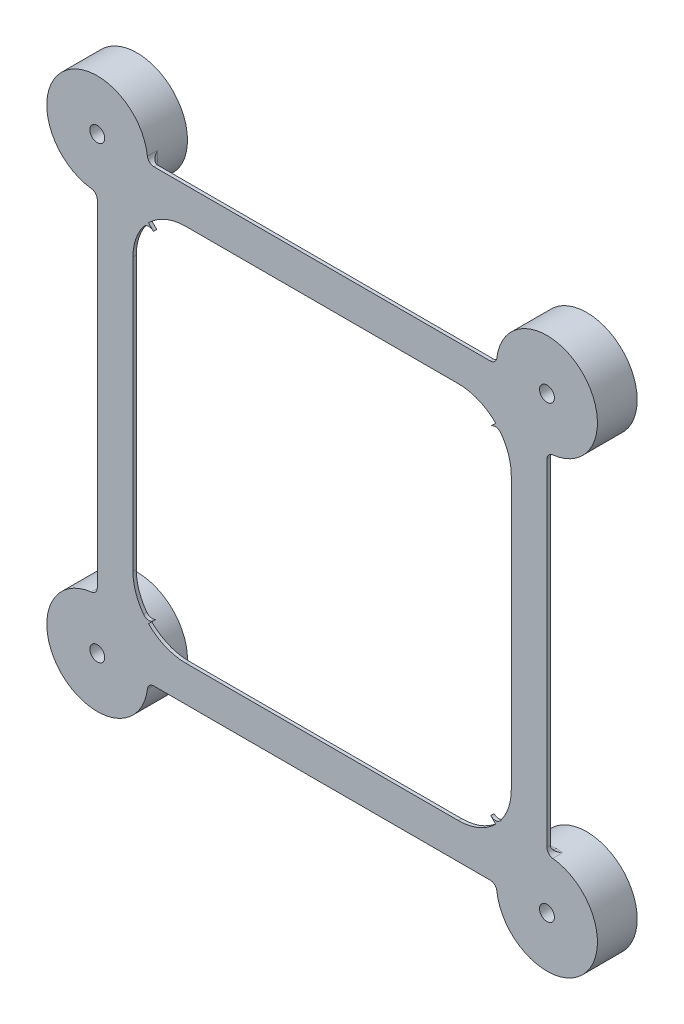
SolidWorks part; units mm, degrees
ref_plane "Front Plane" through (0, 0, 0) normal (0, 0, 1) x (1, 0, 0)
ref_plane "Top Plane" through (0, 0, 0) normal (0, 1, 0) x (1, 0, 0)
ref_plane "Right Plane" through (0, 0, 0) normal (1, 0, 0) x (0, 0, -1)
sketch "Sketch1" plane through (0, 0, 0) normal (0, 0, 1) x (1, 0, 0)
  line L0 (-107.7631, -107.7631) -> (-107.7631, 107.7631) construction
  line L1 (-107.7631, 107.7631) -> (107.7631, 107.7631) construction
  line L2 (107.7631, 107.7631) -> (107.7631, -107.7631) construction
  line L3 (107.7631, -107.7631) -> (-107.7631, -107.7631) construction
  line L4 (-107.7631, -107.7631) -> (107.7631, 107.7631) construction
  circle A0 centre (-107.7631, 107.7631) radius 24.1935
  circle A1 centre (107.7631, 107.7631) radius 24.1935
  circle A2 centre (107.7631, -107.7631) radius 24.1935
  circle A3 centre (-107.7631, -107.7631) radius 24.1935
  circle A9 centre (-107.7631, 107.7631) radius 3.5719
  circle A10 centre (107.7631, 107.7631) radius 3.5719
  circle A11 centre (107.7631, -107.7631) radius 3.5719
  circle A12 centre (-107.7631, -107.7631) radius 3.5719
  point P2 (0, 0)
  dimension "D1" = 7.1437
  dimension "D2" = 48.387
  dimension "D3" = 215.5261
extrude "Boss-Extrude1" add sketch "Sketch1" along normal blind 19.05
sketch "Sketch2" plane through (0, 0, 19.05) normal (0, 0, 1) x (1, 0, 0)
  line L12 (107.7631, 107.7631) -> (-107.7631, -107.7631) construction
  line L13 (-95.0631, 107.7631) -> (95.0631, 107.7631)
  line L14 (-107.7631, 95.0631) -> (-107.7631, -95.0631)
  line L15 (-95.0631, -107.7631) -> (95.0631, -107.7631)
  line L16 (107.7631, 95.0631) -> (107.7631, -95.0631)
  line L17 (-65.2557, 90.6557) -> (65.2557, 90.6557)
  line L18 (-90.6557, 65.2557) -> (-90.6557, -65.2557)
  line L19 (-65.2557, -90.6557) -> (65.2557, -90.6557)
  line L20 (90.6557, 65.2557) -> (90.6557, -65.2557)
  circle A2 centre (-107.7631, 107.7631) radius 24.1935 construction
  circle A3 centre (107.7631, -107.7631) radius 24.1935 construction
  circle A7 centre (-107.7631, -107.7631) radius 24.1935 construction
  circle A8 centre (107.7631, 107.7631) radius 24.1935 construction
  arc A9 (-107.7631, -95.0631) -> (-95.0631, -107.7631) centre (-95.0631, -95.0631) ccw
  arc A10 (95.0631, -107.7631) -> (107.7631, -95.0631) centre (95.0631, -95.0631) ccw
  arc A11 (95.0631, 107.7631) -> (107.7631, 95.0631) centre (95.0631, 95.0631) cw
  arc A12 (-95.0631, 107.7631) -> (-107.7631, 95.0631) centre (-95.0631, 95.0631) ccw
  arc A13 (-90.6557, -65.2557) -> (-65.2557, -90.6557) centre (-65.2557, -65.2557) ccw
  arc A14 (65.2557, -90.6557) -> (90.6557, -65.2557) centre (65.2557, -65.2557) ccw
  arc A15 (65.2557, 90.6557) -> (90.6557, 65.2557) centre (65.2557, 65.2557) cw
  arc A16 (-65.2557, 90.6557) -> (-90.6557, 65.2557) centre (-65.2557, 65.2557) ccw
  point P24 (107.7631, -107.7631)
  point P32 (-107.7631, 107.7631)
  point P35 (-90.6557, -90.6557)
  point P38 (90.6557, -90.6557)
  point P41 (90.6557, 90.6557)
  point P44 (-90.6557, 90.6557)
  dimension "D1" = 12.7
  dimension "D2" = 25.4
extrude "Boss-Extrude2" add sketch "Sketch2" against normal blind 1.5875
fillet "Fillet1" radius 3.175 12 edges at (-90.6557, 90.6557, 17.4625) (90.6557, 90.6557, 17.4625) (90.6557, -90.6557, 17.4625) (-90.6557, -90.6557, 17.4625) (-107.7631, -83.5696, 18.2563) (83.5696, 107.7631, 18.2563) (-107.7631, 83.5696, 18.2563) (83.5696, -107.7631, 18.2563) (107.7631, 83.5696, 18.2563) (-83.5696, 107.7631, 18.2563) (107.7631, -83.5696, 18.2563) (-83.5696, -107.7631, 18.2563)
sketch "Sketch3" plane through (0, 0, 19.05) normal (0, 0, 1) x (1, 0, 0)
  line L0 (0, 0) -> (0, -32.5923) construction
  line L1 (-80.8099, 80.8099) -> (-83.2162, 83.2162)
  line L2 (80.8099, -80.8099) -> (83.2162, -83.2162)
  line L3 (80.8099, 80.8099) -> (83.2162, 83.2162)
  line L4 (-80.8099, -80.8099) -> (-83.2162, -83.2162)
  arc A1 (90.6557, 65.2557) -> (65.2557, 90.6557) centre (65.2557, 65.2557) ccw construction
  arc A3 (65.2557, -90.6557) -> (90.6557, -65.2557) centre (65.2557, -65.2557) ccw construction
  arc A4 (80.8099, -80.8099) -> (85.5978, -80.4662) centre (83.055, -78.5649) ccw
  arc A5 (83.2162, -83.2162) -> (85.5978, -80.4662) centre (65.2557, -65.2557) ccw
  arc A6 (85.5978, 80.4662) -> (80.8099, 80.8099) centre (83.055, 78.5649) ccw
  arc A7 (85.5978, 80.4662) -> (83.2162, 83.2162) centre (65.2557, 65.2557) ccw
  arc A8 (-85.5978, 80.4662) -> (-83.2162, 83.2162) centre (-65.2557, 65.2557) cw
  arc A9 (-85.5978, 80.4662) -> (-80.8099, 80.8099) centre (-83.055, 78.5649) cw
  arc A10 (-83.2162, -83.2162) -> (-85.5978, -80.4662) centre (-65.2557, -65.2557) cw
  arc A11 (-80.8099, -80.8099) -> (-85.5978, -80.4662) centre (-83.055, -78.5649) cw
  dimension "D1" = 6.35
extrude "Boss-Extrude3" add sketch "Sketch3" against normal up to surface (1.5875 mm away) up to face at (0, 0, 17.4625)
